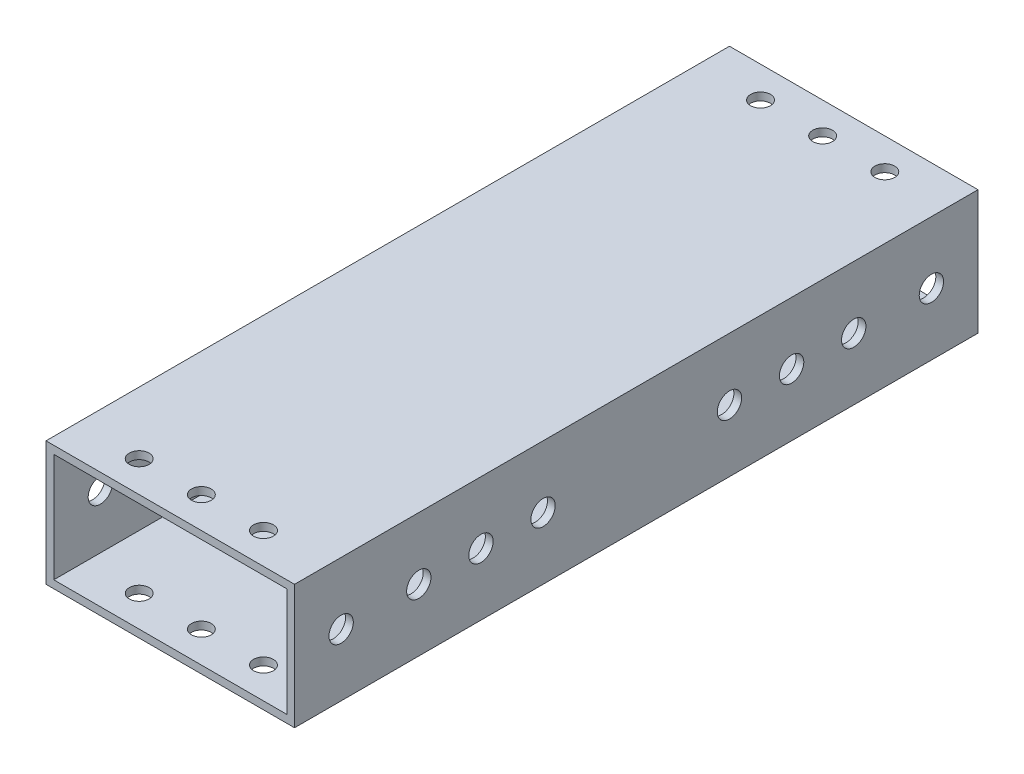
SolidWorks part; units mm, degrees
material "6061-T6 (SS)"
ref_plane "Front Plane" through (0, 0, 0) normal (0, 0, 1) x (1, 0, 0)
ref_plane "Top Plane" through (0, 0, 0) normal (0, 1, 0) x (1, 0, 0)
ref_plane "Right Plane" through (0, 0, 0) normal (1, 0, 0) x (0, 0, -1)
sketch "Sketch1" plane through (0, 0, 0) normal (0, 0, 1) x (1, 0, 0)
  line L0 (-23.8125, 11.1125) -> (23.8125, 11.1125)
  line L1 (-25.4, -12.7) -> (25.4, -12.7)
  line L2 (-25.4, -12.7) -> (-25.4, 12.7)
  line L3 (-25.4, 12.7) -> (25.4, 12.7)
  line L4 (25.4, -12.7) -> (25.4, 12.7)
  line L5 (-25.4, -12.7) -> (25.4, 12.7) construction
  line L6 (-25.4, 12.7) -> (25.4, -12.7) construction
  line L7 (23.8125, -11.1125) -> (23.8125, 11.1125)
  line L8 (-23.8125, -11.1125) -> (23.8125, -11.1125)
  line L9 (-23.8125, -11.1125) -> (-23.8125, 11.1125)
  point P0 (0, 0)
  dimension "D1" = 50.8
  dimension "D2" = 25.4
  dimension "D3" = 1.5875
extrude "Boss-Extrude1" add sketch "Sketch1" along normal mid plane 139.7
sketch "Sketch2" plane through (0, 12.7, 0) normal (0, 1, 0) x (1, 0, 0)
  line L0 (25.4, 69.85) -> (-25.4, 69.85) construction
  line L1 (25.4, 0) -> (-25.4, 0) construction
  line L2 (25.4, -69.85) -> (25.4, 69.85) construction
  line L3 (-25.4, -69.85) -> (-25.4, 69.85) construction
  circle A0 centre (-12.7, 63.5) radius 2.0193
  circle A1 centre (0, 63.5) radius 2.0193
  circle A2 centre (12.7, 63.5) radius 2.0193
  circle A3 centre (12.7, -63.5) radius 2.0193
  circle A4 centre (0, -63.5) radius 2.0193
  circle A5 centre (-12.7, -63.5) radius 2.0193
  dimension "D1" = 4.0386
  dimension "D2" = 12.7
  dimension "D3" = 12.7
  dimension "D4" = 6.35
extrude "Cut-Extrude1" cut sketch "Sketch2" against normal through all
sketch "Sketch3" plane through (25.4, 0, 0) normal (1, 0, 0) x (0, 0, -1)
  line L0 (0, 12.7) -> (0, -12.7) construction
  line L1 (-69.85, 12.7) -> (69.85, 12.7) construction
  line L2 (-69.85, -12.7) -> (69.85, -12.7) construction
  line L3 (-69.85, -12.7) -> (-69.85, 12.7) construction
  circle A0 centre (-60.325, 0) radius 2.4892
  circle A1 centre (60.325, 0) radius 2.4892
  circle A2 centre (-44.45, 0) radius 2.4892
  circle A3 centre (-31.75, 0) radius 2.4892
  circle A4 centre (31.75, 0) radius 2.4892
  circle A5 centre (44.45, 0) radius 2.4892
  circle A6 centre (-19.05, 0) radius 2.4892
  circle A7 centre (19.05, 0) radius 2.4892
  dimension "D1" = 12.7
  dimension "D3" = 4.9784
  dimension "D2" = 9.525
  dimension "D4" = 15.875
  dimension "D5" = 12.7
extrude "Cut-Extrude2" cut sketch "Sketch3" against normal through all
